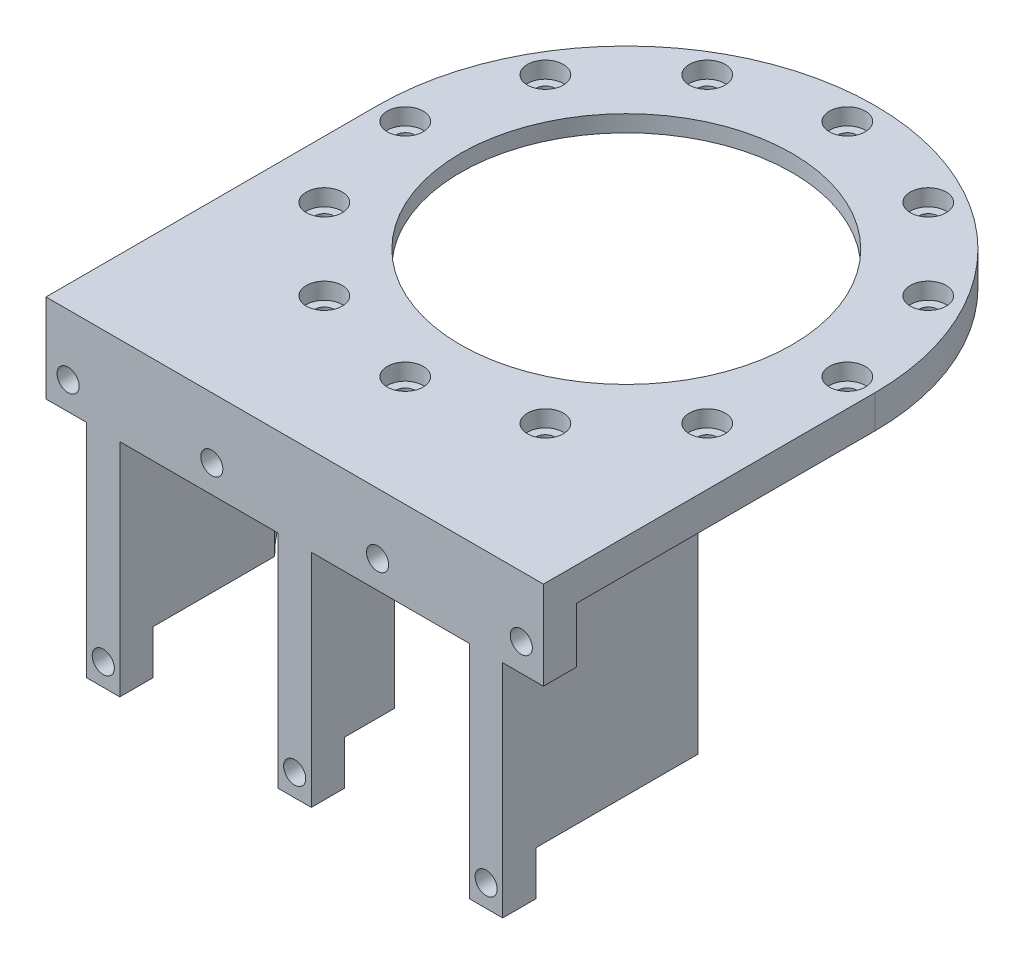
SolidWorks part; units mm, degrees
ref_plane "Front Plane" through (0, 0, 0) normal (0, 0, 1) x (1, 0, 0)
ref_plane "Top Plane" through (0, 0, 0) normal (0, 1, 0) x (1, 0, 0)
ref_plane "Right Plane" through (0, 0, 0) normal (1, 0, 0) x (0, 0, -1)
sketch "Sketch1" plane through (0, 0, 0) normal (0, 1, 0) x (1, 0, 0)
  line L0 (0, 0) -> (0, 52.0165) construction
  circle A0 centre (0, 0) radius 45
  circle A1 centre (0, 0) radius 30
  circle A2 centre (0, 0) radius 40 construction
  circle A3 centre (0, 40) radius 1.75
  circle A4 centre (0, 0) radius 36 construction
  circle A5 centre (20, 34.641) radius 1.75
  circle A6 centre (34.641, 20) radius 1.75
  circle A7 centre (40, 0) radius 1.75
  circle A8 centre (34.641, -20) radius 1.75
  circle A9 centre (20, -34.641) radius 1.75
  circle A10 centre (0, -40) radius 1.75
  circle A11 centre (-20, -34.641) radius 1.75
  circle A12 centre (-34.641, -20) radius 1.75
  circle A13 centre (-40, 0) radius 1.75
  circle A14 centre (-34.641, 20) radius 1.75
  circle A15 centre (-20, 34.641) radius 1.75
  point P21 (0, 0)
  point P34 (0, 0)
  point P48 (0, 0)
  point P72 (0, 0)
  dimension "D1" = 90
  dimension "D2" = 60
  dimension "D4" = 3.5
  dimension "D5" = 72
  dimension "D6" = 12
  dimension "D3" = 80
extrude "Boss-Extrude1" add sketch "Sketch1" along normal blind 6
sketch "Sketch2" plane through (0, 0, 0) normal (0, -1, 0) x (1, 0, 0)
  circle A0 centre (0, 0) radius 36
  dimension "D1" = 72
extrude "Cut-Extrude1" cut sketch "Sketch2" against normal blind 3
sketch "Sketch3" plane through (0, 6, 0) normal (0, 1, 0) x (1, 0, 0)
  line L0 (0, 0) -> (49.8808, 0) construction
  circle A0 centre (40, 0) radius 3.25
  circle A1 centre (34.641, -20) radius 3.25
  circle A2 centre (20, -34.641) radius 3.25
  circle A3 centre (0, -40) radius 3.25
  circle A4 centre (-20, -34.641) radius 3.25
  circle A5 centre (-34.641, -20) radius 3.25
  circle A6 centre (-40, 0) radius 3.25
  circle A7 centre (-34.641, 20) radius 3.25
  circle A8 centre (-20, 34.641) radius 3.25
  circle A9 centre (0, 40) radius 3.25
  circle A10 centre (20, 34.641) radius 3.25
  circle A11 centre (34.641, 20) radius 3.25
  point P30 (0, 0)
  dimension "D1" = 6.5
  dimension "D2" = 12
extrude "Cut-Extrude2" cut sketch "Sketch3" against normal blind 3
sketch "Sketch4" plane through (0, 0, 0) normal (0, -1, 0) x (1, 0, 0)
  line L0 (45, 0) -> (45, 60)
  line L1 (-45, 0) -> (-45, 60)
  line L2 (45, 60) -> (-45, 60)
  line L3 (45, 0) -> (-45, 0) construction
  circle A1 centre (0, 0) radius 45 construction
  arc A2 (45, 0) -> (-45, 0) centre (0, 0) ccw
  dimension "D1" = 60
  dimension "D2" = 90
extrude "Boss-Extrude4" add sketch "Sketch4" against normal blind 6
sketch "Sketch5" plane through (0, 0, 0) normal (0, -1, 0) x (1, 0, 0)
  line L0 (45, 0) -> (45, 60) construction
  line L1 (45, 54) -> (-45, 54)
  line L2 (45, 54) -> (45, 60)
  line L3 (45, 60) -> (-45, 60)
  line L4 (-45, 54) -> (-45, 60)
  dimension "D1" = 6
extrude "Boss-Extrude6" add sketch "Sketch5" along normal blind 10
sketch "Sketch6" plane through (0, 0, 0) normal (0, -1, 0) x (1, 0, 0)
  line L0 (0, 0) -> (0, 68.4249) construction
  line L1 (34.641, 20) -> (34.641, 68.4249) construction
  line L2 (37.641, 24.6608) -> (37.641, 60)
  line L3 (45, 60) -> (-45, 60) construction
  line L4 (37.641, 60) -> (31.641, 60)
  line L5 (31.641, 60) -> (31.641, 31.9976)
  line L6 (-3, 60) -> (3, 60)
  line L7 (3, 60) -> (3, 44.8999)
  line L8 (-3, 60) -> (-3, 44.8999)
  line L9 (-31.641, 60) -> (-31.641, 31.9976)
  line L10 (-37.641, 60) -> (-31.641, 60)
  line L11 (-37.641, 24.6608) -> (-37.641, 60)
  arc A0 (37.641, 24.6608) -> (31.641, 31.9976) centre (0, 0) ccw
  arc A1 (3, 44.8999) -> (-3, 44.8999) centre (0, 0) ccw
  arc A2 (-37.641, 24.6608) -> (-31.641, 31.9976) centre (0, 0) cw
  point P17 (0, 60)
  dimension "D1" = 90
  dimension "D2" = 3
  dimension "D3" = 3
  dimension "D4" = 3
extrude "Boss-Extrude7" add sketch "Sketch6" along normal blind 50
sketch "Sketch7" plane through (37.641, 0, 0) normal (1, 0, 0) x (0, 0, -1)
  line L0 (-24.6608, -42) -> (-54, -42)
  line L1 (-24.6608, -50) -> (-24.6608, 0) construction
  line L2 (-54, -42) -> (-54, -50)
  line L3 (-24.6608, -50) -> (-60, -50) construction
  line L4 (-60, -50) -> (-60, -10) construction
  line L5 (-24.6608, -42) -> (-24.6608, -50)
  line L6 (-24.6608, -50) -> (-54, -50)
  dimension "D1" = 6
  dimension "D2" = 8
extrude "Cut-Extrude3" cut sketch "Sketch7" against normal through all
sketch "Sketch8" plane through (0, 0, 54) normal (0, 0, -1) x (-1, 0, 0)
  line L0 (45, -5) -> (-45, -5) construction
  line L1 (45, -10) -> (45, 0) construction
  line L2 (-45, -10) -> (-45, 0) construction
  line L3 (34.641, -50) -> (34.641, -42) construction
  line L4 (37.641, -50) -> (31.641, -50) construction
  line L5 (37.641, -42) -> (31.641, -42) construction
  line L6 (0, -50) -> (0, -42) construction
  line L7 (3, -50) -> (-3, -50) construction
  line L8 (3, -42) -> (-3, -42) construction
  line L9 (-34.641, -50) -> (-34.641, -42) construction
  line L10 (-31.641, -50) -> (-37.641, -50) construction
  line L11 (-37.641, -42) -> (-31.641, -42) construction
  circle A0 centre (41, -5) radius 2
  circle A1 centre (34.641, -46) radius 2
  circle A2 centre (0, -46) radius 2
  circle A3 centre (15, -5) radius 2
  circle A4 centre (-34.641, -46) radius 2
  circle A5 centre (-41, -5) radius 2
  circle A6 centre (-15, -5) radius 2
  point P32 (0, -5)
  dimension "D1" = 4
  dimension "D3" = 4
  dimension "D5" = 4
  dimension "D7" = 4
  dimension "D2" = 4
  dimension "D4" = 4
  dimension "D6" = 4
  dimension "D8" = 15
extrude "Cut-Extrude5" cut sketch "Sketch8" against normal through all
